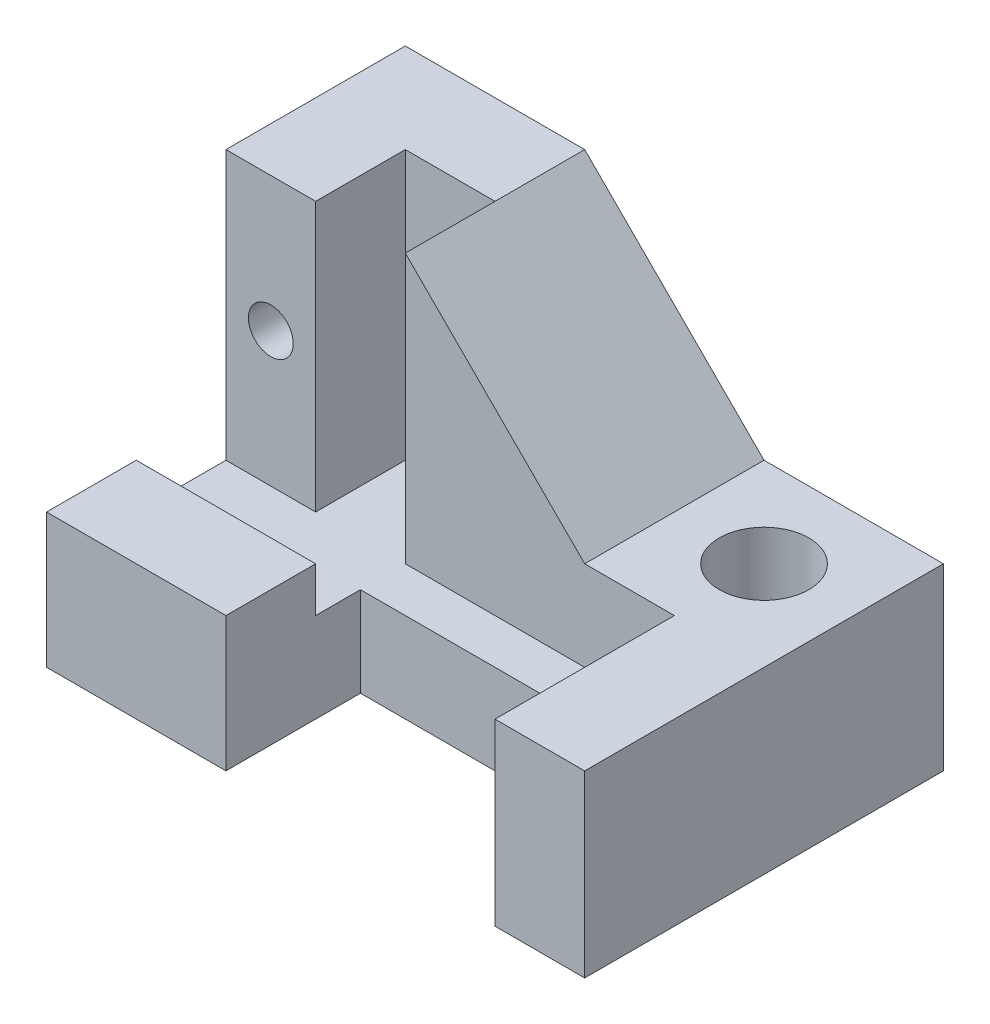
SolidWorks part; units mm, degrees
ref_plane "Front Plane" through (0, 0, 0) normal (0, 0, 1) x (1, 0, 0)
ref_plane "Top Plane" through (0, 0, 0) normal (0, 1, 0) x (1, 0, 0)
ref_plane "Right Plane" through (0, 0, 0) normal (1, 0, 0) x (0, 0, -1)
sketch "Sketch1" plane through (0, 0, 0) normal (0, 1, 0) x (1, 0, 0)
  line L1 (0, 0) -> (3, 0)
  line L2 (0, 0) -> (0, 2)
  line L3 (0, 2) -> (3, 2)
  line L4 (3, 0) -> (3, 2)
  dimension "D1" = 2
  dimension "D2" = 3
extrude "Boss-Extrude1" add sketch "Sketch1" along normal blind 0.5
sketch "Sketch4" plane through (0, 0.5, 0) normal (0, 1, 0) x (1, 0, 0)
  line L0 (0, 2) -> (0, 1)
  line L1 (0, 2) -> (0, 0) construction
  line L2 (0, 1) -> (0.5, 1)
  line L3 (0.5, 1) -> (0.5, 1.5)
  line L4 (0.5, 1.5) -> (1, 1.5)
  line L5 (0, 2) -> (1, 2)
  line L6 (3, 2) -> (0, 2) construction
  line L7 (2, 2) -> (3, 2)
  line L8 (0, 0) -> (1, 0)
  line L9 (0, 0) -> (0, 0.5)
  line L10 (0, 0.5) -> (1, 0.5)
  line L11 (1, 0) -> (1, 0.5)
  line L12 (1, 0) -> (2.5, 0)
  line L13 (1, 0) -> (1, 0.75)
  line L14 (1, 0.75) -> (2.5, 0.75)
  line L15 (2.5, 0) -> (2.5, 0.75)
  line L16 (1, 2) -> (2, 2)
  line L17 (1, 2) -> (1, 1)
  line L18 (1, 1) -> (2, 1)
  line L19 (2, 2) -> (2, 1) construction
  line L20 (3, 2) -> (3, 0)
  line L21 (3, 0) -> (2.5, 0)
  line L22 (2.5, 0.75) -> (2.5, 1)
  line L23 (2.5, 1) -> (2, 1)
  line M19 (0, 2) -> (0, 0)
  line M20 (0, 0) -> (3, 0)
  line M21 (3, 0) -> (3, 2)
  line M22 (3, 2) -> (0, 2)
  dimension "D1" = 1
  dimension "D2" = 0.5
  dimension "D3" = 0.5
  dimension "D4" = 1
  dimension "D5" = 1.5
  dimension "D6" = 0.75
  dimension "D7" = 1
  dimension "D8" = 1
extrude "Cut-Extrude4" cut sketch "Sketch4" against normal through all both and the other way through all contours L15 L14 L13 L11 M20 region at (1.75, 0.5, -0.375)
extrude "Boss-Extrude2" add sketch "Sketch4<6>" along normal blind 0.25 contours L8 L9 L10 L11
sketch "Sketch4<6>" plane through (0, 0.5, 0) normal (0, 1, 0) x (1, 0, 0) same geometry as "Sketch4"
extrude "Boss-Extrude3" add sketch "Sketch4<9>" along normal blind 1.5 contours L17 L2 L3 L4 M22 M19 | L19 L17 L18 M22 | L19 L23 L22 L15 M22 M20 M21 region at (0.4167, 0.5, -1.5833) region at (1.5, 0.5, -1.5) region at (2.5833, 0.5, -1.1667)
sketch "Sketch4<9>" plane through (0, 0.5, 0) normal (0, 1, 0) x (1, 0, 0) same geometry as "Sketch4"
sketch "Sketch8" plane through (0, 0, 0) normal (0, 0, 1) x (1, 0, 0)
  line L0 (1, 2) -> (2, 1)
  line L1 (2, 1) -> (3, 1)
  line L2 (3, 2) -> (3, 0) construction
  line L3 (3, 1) -> (3, 2)
  line L4 (3, 2) -> (1, 2)
  dimension "D1" = 45
  dimension "D2" = 1
extrude "Cut-Extrude5" cut sketch "Sketch8" against normal through all
sketch "Sketch9" plane through (0, 1, 0) normal (0, 1, 0) x (1, 0, 0)
  line L1 (2, 2) -> (2, 1) construction
  line L2 (2, 2) -> (3, 2) construction
  circle A0 centre (2.5, 1.5) radius 0.25
  point P6 (2, 1.5)
  point P7 (2.5, 2)
  dimension "D1" = 0.5
extrude "Cut-Extrude6" cut sketch "Sketch9" against normal through all
sketch "Sketch10" plane through (0, 0, -1) normal (0, 0, 1) x (1, 0, 0)
  line L0 (0, 2) -> (0.5, 2) construction
  line L1 (0, 2) -> (0, 0.5) construction
  circle A0 centre (0.25, 1.25) radius 0.125
  point P4 (0.25, 2)
  point P7 (0, 1.25)
  dimension "D1" = 0.25
extrude "Cut-Extrude7" cut sketch "Sketch10" against normal through all
